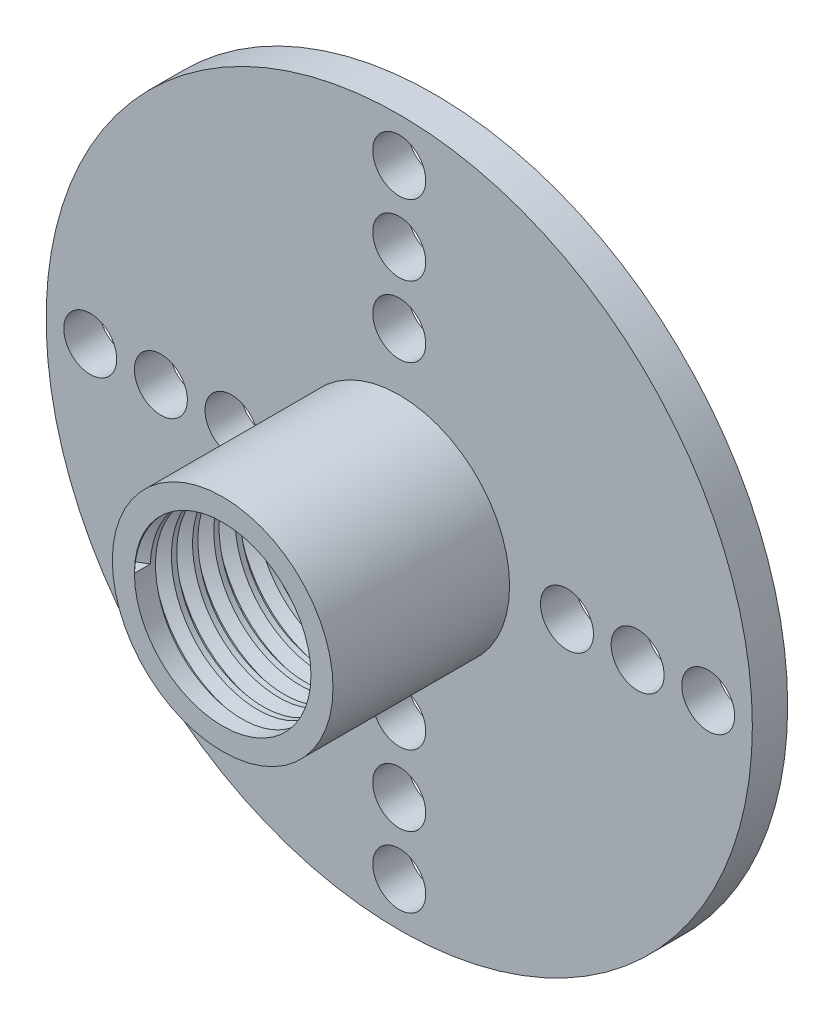
SolidWorks part; units mm, degrees
ref_plane "Front" through (0, 0, 0) normal (0, 0, 1) x (1, 0, 0)
ref_plane "Top" through (0, 0, 0) normal (0, 1, 0) x (1, 0, 0)
ref_plane "Right" through (0, 0, 0) normal (1, 0, 0) x (0, 0, -1)
sketch "Sketch1" plane through (0, 0, 0) normal (0, 0, 1) x (1, 0, 0)
  line L0 (0, 0) -> (4.75, 0) construction
  circle A0 centre (0, 0) radius 1.75
  circle A1 centre (0, 0) radius 0.84
  circle A2 centre (0, 0) radius 10
  circle A3 centre (4.75, 0) radius 0.75
  circle A4 centre (6.75, 0) radius 0.75
  circle A5 centre (8.75, 0) radius 0.75
  circle A6 centre (0, -4.75) radius 0.75
  circle A7 centre (0, -6.75) radius 0.75
  circle A8 centre (0, -8.75) radius 0.75
  circle A9 centre (-4.75, 0) radius 0.75
  circle A10 centre (-6.75, 0) radius 0.75
  circle A11 centre (-8.75, 0) radius 0.75
  circle A12 centre (0, 4.75) radius 0.75
  circle A13 centre (0, 6.75) radius 0.75
  circle A14 centre (0, 8.75) radius 0.75
  point P32 (0, 0)
  dimension "D1" = 20
  dimension "D2" = 1.5
  dimension "D6" = 1.68
  dimension "D7" = 3.5
  dimension "D3" = 4.75
  dimension "D4" = 3
  dimension "D5" = 4
extrude "Boss-Extrude1" add sketch "Sketch1" along normal blind 1 contours A2 A14 A13 A12 A11 A10 A9 A8 A7 A6 A5 A4 A0 A3 region at (-9.7172, 0, 0)
extrude "Boss-Extrude2" add sketch "Sketch1<3>" along normal blind 0.5 from offset 0.5 contours A1 A0 region at (-1.7005, 0, 0)
sketch "Sketch1<3>" plane through (0, 0, 0) normal (0, 0, 1) x (1, 0, 0) same geometry as "Sketch1"
sketch "Sketch2" plane through (0, 0, 1) normal (0, 0, 1) x (1, 0, 0)
  circle A0 centre (0, 0) radius 3.125
  circle A1 centre (0, 0) radius 2.5
  dimension "D1" = 6.25
  dimension "D2" = 5
extrude "Boss-Extrude3" add sketch "Sketch2" along normal blind 5
thread "Thread1" pitch 0.6 method cut profile "Thread Profile1" start angle 0, offset 0, length 4.5, pitch 0.6, diameter 5
ref_plane "Plane1" through (-2.5, 0, 6) normal (0, -1, 0) x (-1, 0, 0)
sketch "Thread Profile1" plane through (-2.5, 0, 6) normal (0, -1, 0) x (-1, 0, 0)
  line L0 (0, 0) -> (0, 0.6) construction
  line L1 (0, 0) -> (0.3248, 0.1875)
  line L2 (0.3248, 0.1875) -> (0.3248, 0.2625)
  line L3 (0.3248, 0.2625) -> (0, 0.45)
  line L4 (0.3248, 0.225) -> (0, 0.225) construction
  line L11 (0, 0) -> (0, 0.45)
  point P2 (0, 0)
  dimension "Pitch" = 0.6
  dimension "Profile_Angle" = 60
  dimension "Profile_Land" = 0.075
  dimension "Profile_Height" = 0.3248
